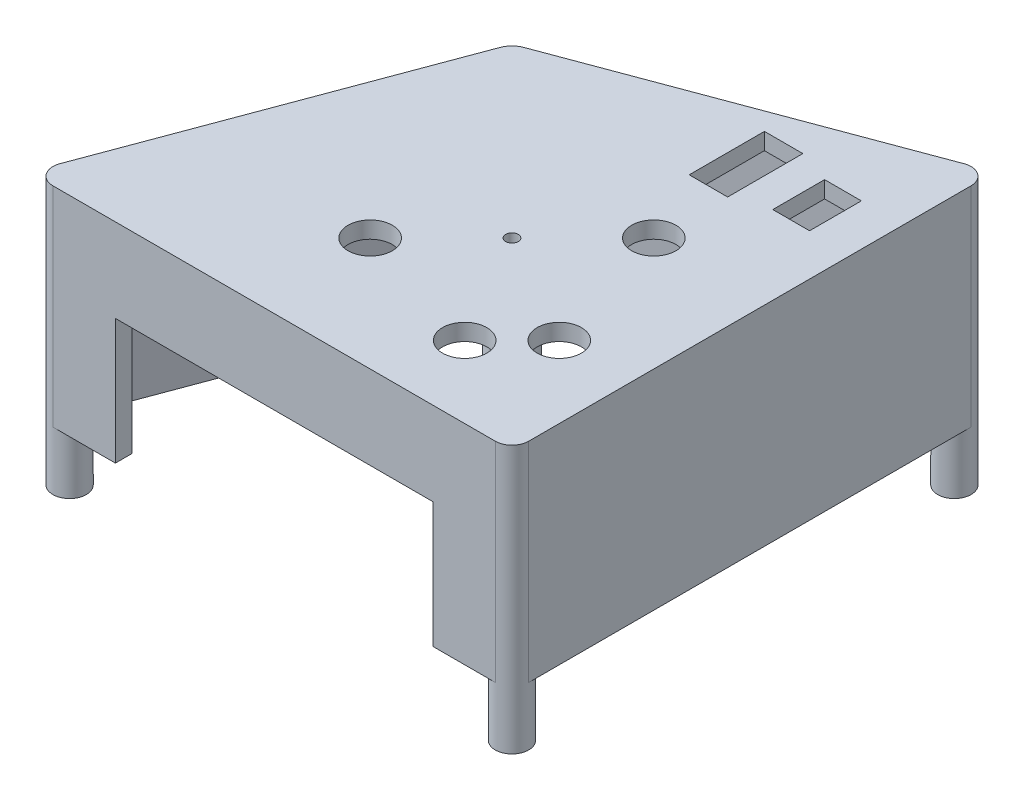
SolidWorks part; units mm, degrees
ref_plane "Front Plane" through (0, 0, 0) normal (0, 0, 1) x (1, 0, 0)
ref_plane "Top Plane" through (0, 0, 0) normal (0, 1, 0) x (1, 0, 0)
ref_plane "Right Plane" through (0, 0, 0) normal (1, 0, 0) x (0, 0, -1)
sketch "Sketch2" plane through (0, 0, 0) normal (0, 1, 0) x (1, 0, 0)
  line L0 (3.366, 5.9446) -> (70.5858, 5.9446)
  line L1 (73.1258, 8.4846) -> (73.1258, 75.7043)
  line L2 (69.6998, 78.0848) -> (20.9849, 59.9535)
  line L3 (19.1168, 58.0854) -> (0.9856, 9.3705)
  arc A0 (73.1258, 75.7043) -> (69.6998, 78.0848) centre (70.5858, 75.7043) ccw
  arc A1 (3.366, 5.9446) -> (0.9856, 9.3705) centre (3.366, 8.4846) cw
  arc A2 (70.5858, 5.9446) -> (73.1258, 8.4846) centre (70.5858, 8.4846) ccw
  arc A3 (20.9849, 59.9535) -> (19.1168, 58.0854) centre (22.0924, 56.9779) ccw
  dimension "D1" = 2.54
  dimension "D2" = 3.175
  dimension "D3" = 67.2197
  dimension "D4" = 67.2197
  dimension "D5" = 68.58
  dimension "D6" = 51.9835
  dimension "D7" = 51.9835
extrude "Boss-Extrude1" add sketch "Sketch2" along normal blind 31.75
shell "Shell1" thickness 2.54 removed face at (41.38, 0, -37.6904)
sketch "Sketch3" plane through (0, 31.75, 0) normal (0, 1, 0) x (1, 0, 0)
  circle A0 centre (70.5858, 8.4846) radius 2.54
  circle A1 centre (70.5858, 75.7043) radius 2.54
  circle A2 centre (3.366, 8.4846) radius 2.54
  circle A3 centre (22.0924, 56.9779) radius 3.175
  dimension "D1" = 5.08
  dimension "D2" = 5.08
  dimension "D3" = 5.08
  dimension "D4" = 6.35
extrude "Boss-Extrude2" add sketch "Sketch3" against normal blind 40.64
sketch "Sketch4" plane through (0, 0, -5.9446) normal (0, 0, 1) x (1, 0, 0)
  line L0 (3.366, 0) -> (70.5858, 0) construction
  line L1 (61.1243, 0) -> (12.8643, 0)
  line L2 (61.1243, 0) -> (61.1243, 19.05)
  line L3 (61.1243, 19.05) -> (12.8643, 19.05)
  line L4 (12.8643, 0) -> (12.8643, 19.05)
  dimension "D1" = 19.05
  dimension "D2" = 48.26
  dimension "D3" = 9.4615
  dimension "D4" = 9.4982
extrude "Cut-Extrude1" cut sketch "Sketch4" against normal up to next
sketch "Sketch5" plane through (0, 31.75, 0) normal (0, 1, 0) x (1, 0, 0)
  line L0 (73.1258, 8.4846) -> (73.1258, 75.7043) construction
  line L1 (61.1878, 57.5108) -> (66.7758, 57.5108)
  line L2 (61.1878, 57.5108) -> (61.1878, 65.3848)
  line L3 (61.1878, 65.3848) -> (66.7758, 65.3848)
  line L4 (66.7758, 57.5108) -> (66.7758, 65.3848)
  dimension "D1" = 7.874
  dimension "D2" = 5.588
  dimension "D3" = 6.35
  dimension "D4" = 12.7
extrude "Cut-Extrude2" cut sketch "Sketch5" against normal up to next
sketch "Sketch6" plane through (0, 31.75, 0) normal (0, 1, 0) x (1, 0, 0)
  line L1 (56.1078, 55.7328) -> (50.2658, 55.7328)
  line L2 (56.1078, 55.7328) -> (56.1078, 67.1628)
  line L3 (56.1078, 67.1628) -> (50.2658, 67.1628)
  line L4 (50.2658, 55.7328) -> (50.2658, 67.1628)
  line L5 (61.1878, 65.3848) -> (61.1878, 57.5108) construction
  point P4 (56.1078, 61.4478)
  point P7 (61.1878, 61.4478)
  dimension "D1" = 5.842
  dimension "D2" = 11.43
  dimension "D3" = 5.08
extrude "Cut-Extrude3" cut sketch "Sketch6" against normal up to next
sketch "Sketch7" plane through (0, 31.75, 0) normal (0, 1, 0) x (1, 0, 0)
  line L0 (72.3818, 6.6885) -> (19.8473, 59.223) construction
  line L1 (62.1792, 24.0754) -> (54.995, 16.8912) construction
  line L2 (34.3404, 23.1774) -> (55.893, 44.73) construction
  arc A0 (70.5858, 5.9446) -> (73.1258, 8.4846) centre (70.5858, 8.4846) ccw construction
  arc A1 (20.9849, 59.9535) -> (19.1168, 58.0854) centre (22.0924, 56.9779) ccw construction
  circle A2 centre (54.995, 16.8912) radius 3.3655
  circle A3 centre (62.1792, 24.0754) radius 3.3655
  circle A6 centre (34.3404, 23.1774) radius 3.3655
  circle A7 centre (55.893, 44.73) radius 3.3655
  circle A8 centre (45.1167, 33.9537) radius 0.9525
  dimension "D1" = 6.731
  dimension "D2" = 6.731
  dimension "D7" = 6.731
  dimension "D8" = 6.731
  dimension "D14" = 1.905
  dimension "D3" = 5.08
  dimension "D4" = 5.08
  dimension "D5" = 19.05
  dimension "D6" = 19.05
  dimension "D9" = 21.59
  dimension "D10" = 21.59
  dimension "D11" = 15.24
  dimension "D12" = 15.24
  dimension "D13" = 19.05
extrude "Cut-Extrude4" cut sketch "Sketch7" against normal up to next
